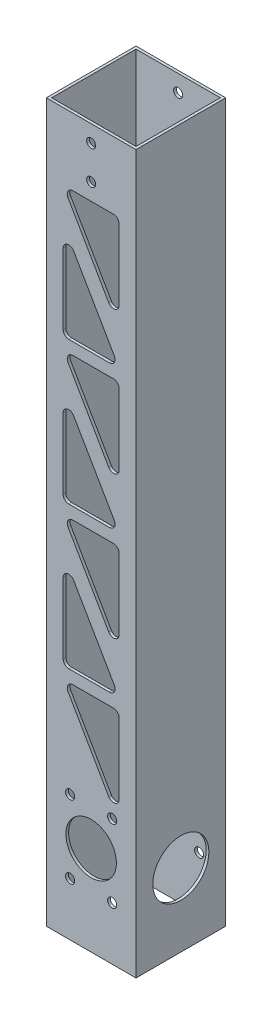
SolidWorks part; units mm, degrees
material "6061 Alloy"
ref_plane "Front Plane" through (0, 0, 0) normal (0, 0, 1) x (1, 0, 0)
ref_plane "Top Plane" through (0, 0, 0) normal (0, 1, 0) x (1, 0, 0)
ref_plane "Right Plane" through (0, 0, 0) normal (1, 0, 0) x (0, 0, -1)
sketch "Sketch1" plane through (0, 0, 0) normal (0, 1, 0) x (1, 0, 0)
  line L1 (25.4, 25.4) -> (-25.4, 25.4)
  line L2 (25.4, 25.4) -> (25.4, -25.4)
  line L3 (25.4, -25.4) -> (-25.4, -25.4)
  line L4 (-25.4, 25.4) -> (-25.4, -25.4)
  line L5 (25.4, 25.4) -> (-25.4, -25.4) construction
  line L6 (25.4, -25.4) -> (-25.4, 25.4) construction
  point P0 (0, 0)
  dimension "D1" = 50.8
extrude "Extrude-Thin1" add sketch "Sketch1" along normal blind 406.4 thin thin type one direction reverse wall 1.524
sketch "Sketch2" plane through (0, 0, 0) normal (0, 0, 1) x (1, 0, 0)
  line L0 (-36.2563, 68.2625) -> (38.5702, 68.2625) construction
  line L1 (-25.4, 0) -> (25.4, 0) construction
  line L2 (-25.4, 50.8) -> (25.4, 50.8) construction
  line L6 (25.4, 406.4) -> (25.4, 0) construction
  line L7 (-25.4, 406.4) -> (-25.4, 0) construction
  line L8 (-11.9062, 30.1778) -> (11.9063, 30.1778) construction
  line L9 (-11.9062, 71.4222) -> (11.9063, 71.4222) construction
  circle A0 centre (0, 50.8) radius 14.3002
  circle A1 centre (0, 50.8) radius 23.8125 construction
  circle A2 centre (-11.9062, 30.1778) radius 2.5908
  circle A3 centre (11.9063, 30.1778) radius 2.5908
  circle A4 centre (11.9063, 71.4222) radius 2.5908
  circle A5 centre (-11.9062, 71.4222) radius 2.5908
  point P11 (0, 50.8)
  dimension "D1" = 28.6004
  dimension "D3" = 17.4625
  dimension "D4" = 47.625
  dimension "D6" = 5.1816
  dimension "D2" = 50.8
  dimension "D5" = 60
extrude "Cut-Extrude1" cut sketch "Sketch2" along normal through all both and the other way through all
sketch "Sketch3" plane through (25.4, 0, 0) normal (1, 0, 0) x (0, 0, -1)
  line L0 (-25.4, 50.8) -> (25.4, 50.8) construction
  line L1 (-25.4, 65.1002) -> (-25.4, 36.4998) construction
  line L3 (25.4, 406.4) -> (25.4, 0) construction
  circle A0 centre (0, 41.275) radius 15.875
  point P9 (0, 50.8)
  dimension "D1" = 31.75
  dimension "D2" = 9.525
extrude "Cut-Extrude2" cut sketch "Sketch3" against normal up to surface (1.524 mm away) up to face at (23.876, 203.2, 0)
sketch "Sketch4" plane through (0, 0, 25.4) normal (0, 0, 1) x (1, 0, 0)
  line L0 (-25.4, 406.4) -> (25.4, 406.4) construction
  circle A0 centre (0, 396.875) radius 2.54
  circle A1 centre (0, 377.825) radius 2.54
  dimension "D1" = 5.08
  dimension "D2" = 9.525
  dimension "D3" = 28.575
hole_wizard "#10 Clearance Hole1" positions "Sketch5" profile "Sketch6" hole size "#10" standard "ANSI Inch" end condition through all
sketch "Sketch5" plane through (0, 0, 25.4) normal (0, 0, 1) x (1, 0, 0)
  point P0 (0, 377.825)
  point P3 (0, 396.875)
sketch "Sketch6" plane through (0, 377.825, 25.4) normal (1, 0, 0) x (0, -1, 0)
  line L0 (0, 0) -> (0, 50.8)
  line L1 (0, 50.8) -> (2.5527, 50.8)
  line L2 (2.5527, 50.8) -> (2.5527, 0)
  line L5 (2.5527, 0) -> (0, 0)
  line L11 (0, -6.35) -> (0, 107.95) construction
  dimension "Thru Hole Dia." = 5.1054
  dimension "Thru Hole Depth" = 50.8
sketch "Sketch7" plane through (0, 0, 25.4) normal (0, 0, 1) x (1, 0, 0)
  line L0 (-15.875, 406.4) -> (-15.875, 0) construction
  line L1 (15.875, 406.4) -> (15.875, 0) construction
  line L2 (-15.875, 0) -> (-25.4, 0) construction
  line L3 (-25.4, 0) -> (25.4, 0) construction
  line L4 (-25.4, 406.4) -> (-25.4, 0) construction
  line L5 (15.875, 0) -> (25.4, 0) construction
  line L6 (-25.4, 406.4) -> (25.4, 406.4) construction
  line L7 (-15.875, 368.3) -> (15.875, 368.3) construction
  line L8 (-15.875, 79.375) -> (15.875, 79.375) construction
  line L9 (-10.3757, 368.3) -> (12.7, 368.3)
  line L10 (15.875, 365.125) -> (15.875, 325.1566)
  line L11 (9.9504, 323.5691) -> (-13.1254, 363.5375)
  line L12 (-12.7, 294.2574) -> (10.3757, 294.2574)
  line L13 (-15.875, 297.4324) -> (-15.875, 337.4007)
  line L14 (-9.9504, 338.9882) -> (13.1254, 299.0199)
  line L15 (2.2219, 317.9053) -> (10.4708, 322.6678) construction
  line L16 (-10.3757, 287.528) -> (12.7, 287.528)
  line L17 (15.875, 284.353) -> (15.875, 244.3846)
  line L18 (9.9504, 242.7971) -> (-13.1254, 282.7655)
  line L19 (-15.875, 216.6604) -> (-15.875, 256.6287)
  line L20 (-12.7, 213.4854) -> (10.3757, 213.4854)
  line L21 (-9.9504, 258.2162) -> (13.1254, 218.2479)
  line L22 (-10.3757, 206.756) -> (12.7, 206.756)
  line L23 (15.875, 203.581) -> (15.875, 163.6126)
  line L24 (9.9504, 162.0251) -> (-13.1254, 201.9935)
  line L25 (-15.875, 135.8884) -> (-15.875, 175.8567)
  line L26 (-12.7, 132.7134) -> (10.3757, 132.7134)
  line L27 (-9.9504, 177.4442) -> (13.1254, 137.4759)
  line L28 (-10.3757, 125.984) -> (12.7, 125.984)
  line L29 (15.875, 122.809) -> (15.875, 82.8406)
  line L30 (9.9504, 81.2531) -> (-13.1254, 121.2215)
  line L34 (-10.3757, 368.3) -> (-10.3757, 287.528) construction
  line L35 (-12.7, 51.9414) -> (10.3757, 51.9414) [skipped]
  line L36 (-15.875, 55.1164) -> (-15.875, 95.0847) [skipped]
  line L37 (-9.9504, 96.6722) -> (13.1254, 56.7039) [skipped]
  arc A0 (-13.1254, 363.5375) -> (-10.3757, 368.3) centre (-10.3757, 365.125) cw
  arc A1 (12.7, 368.3) -> (15.875, 365.125) centre (12.7, 365.125) cw
  arc A2 (15.875, 325.1566) -> (9.9504, 323.5691) centre (12.7, 325.1566) cw
  arc A3 (13.1254, 299.0199) -> (10.3757, 294.2574) centre (10.3757, 297.4324) cw
  arc A4 (-15.875, 337.4007) -> (-9.9504, 338.9882) centre (-12.7, 337.4007) cw
  arc A5 (-15.875, 297.4324) -> (-12.7, 294.2574) centre (-12.7, 297.4324) ccw
  arc A6 (15.875, 244.3846) -> (9.9504, 242.7971) centre (12.7, 244.3846) cw
  arc A7 (-13.1254, 282.7655) -> (-10.3757, 287.528) centre (-10.3757, 284.353) cw
  arc A8 (12.7, 287.528) -> (15.875, 284.353) centre (12.7, 284.353) cw
  arc A9 (-15.875, 256.6287) -> (-9.9504, 258.2162) centre (-12.7, 256.6287) cw
  arc A10 (-15.875, 216.6604) -> (-12.7, 213.4854) centre (-12.7, 216.6604) ccw
  arc A11 (13.1254, 218.2479) -> (10.3757, 213.4854) centre (10.3757, 216.6604) cw
  arc A12 (15.875, 163.6126) -> (9.9504, 162.0251) centre (12.7, 163.6126) cw
  arc A13 (-13.1254, 201.9935) -> (-10.3757, 206.756) centre (-10.3757, 203.581) cw
  arc A14 (12.7, 206.756) -> (15.875, 203.581) centre (12.7, 203.581) cw
  arc A15 (-15.875, 175.8567) -> (-9.9504, 177.4442) centre (-12.7, 175.8567) cw
  arc A16 (-15.875, 135.8884) -> (-12.7, 132.7134) centre (-12.7, 135.8884) ccw
  arc A17 (13.1254, 137.4759) -> (10.3757, 132.7134) centre (10.3757, 135.8884) cw
  arc A18 (15.875, 82.8406) -> (9.9504, 81.2531) centre (12.7, 82.8406) cw
  arc A19 (-13.1254, 121.2215) -> (-10.3757, 125.984) centre (-10.3757, 122.809) cw
  arc A20 (12.7, 125.984) -> (15.875, 122.809) centre (12.7, 122.809) cw
  arc A24 (-15.875, 55.1164) -> (-12.7, 51.9414) centre (-12.7, 55.1164) ccw [skipped]
  arc A25 (13.1254, 56.7039) -> (10.3757, 51.9414) centre (10.3757, 55.1164) cw [skipped]
  arc A26 (-15.875, 95.0847) -> (-9.9504, 96.6722) centre (-12.7, 95.0847) cw [skipped]
  point P31 (15.875, 313.3074)
  point P34 (15.875, 294.2574)
  point P37 (-15.875, 349.25)
  point P40 (-15.875, 294.2574)
  dimension "D5" = 3.175
  dimension "D1" = 9.525
  dimension "D2" = 38.1
  dimension "D3" = 79.375
  dimension "D4" = 30
  dimension "D7" = 80.772
  dimension "D6" = 4
extrude "Cut-Extrude3" cut sketch "Sketch7" against normal through all
